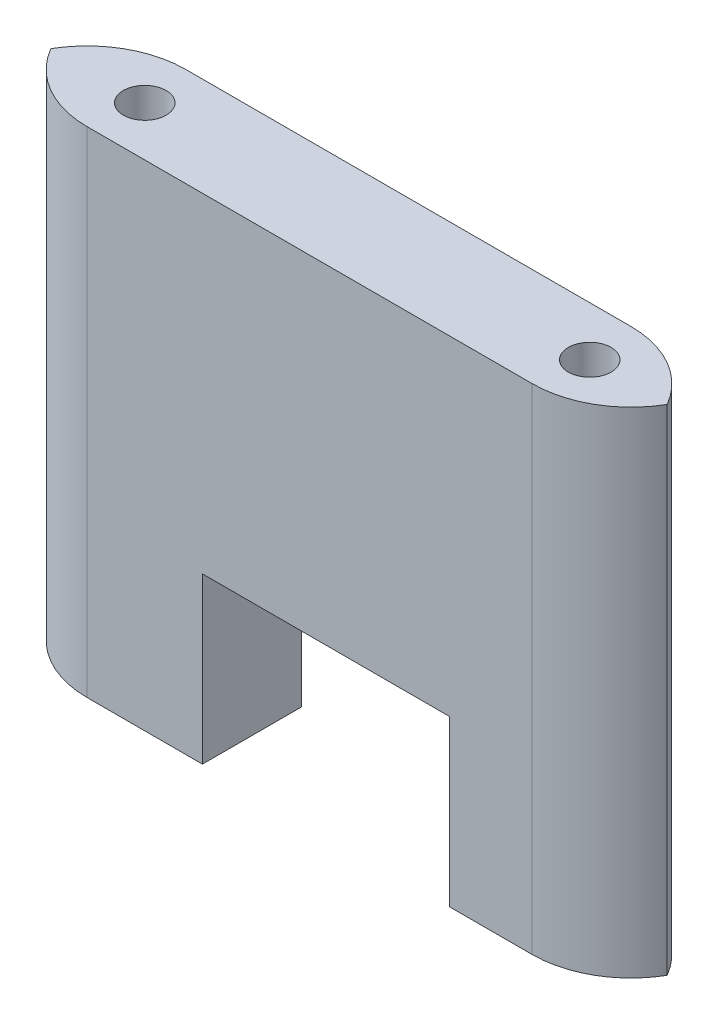
SolidWorks part; units mm, degrees
ref_plane "Front Plane" through (0, 0, 0) normal (0, 0, 1) x (1, 0, 0)
ref_plane "Top Plane" through (0, 0, 0) normal (0, 1, 0) x (1, 0, 0)
ref_plane "Right Plane" through (0, 0, 0) normal (1, 0, 0) x (0, 0, -1)
sketch "Sketch3" plane through (0, 0, 0) normal (0, 0, 1) x (1, 0, 0)
  line L1 (0, 0) -> (49.53, 0)
  line L2 (0, 0) -> (0, 38.1)
  line L3 (0, 38.1) -> (49.53, 38.1)
  line L4 (49.53, 0) -> (49.53, 38.1)
  dimension "D1" = 49.53
  dimension "D2" = 38.1
extrude "Boss-Extrude2" add sketch "Sketch3" along normal blind 7.62
sketch "Sketch4" plane through (0, 0, 7.62) normal (0, 0, 1) x (1, 0, 0)
  line L0 (26.035, 38.1) -> (26.035, -1.144) construction
  line L2 (0, 0) -> (49.53, 0) construction
  line L3 (16.51, 12.7) -> (35.56, 12.7)
  line L4 (16.51, 12.7) -> (16.51, 0)
  line L5 (16.51, 0) -> (35.56, 0)
  line L6 (35.56, 12.7) -> (35.56, 0)
  line L7 (16.51, 12.7) -> (35.56, 0) construction
  line L8 (16.51, 0) -> (35.56, 12.7) construction
  point P1 (26.035, 18.478)
  point P2 (26.035, 6.35)
  dimension "D1" = 26.035
  dimension "D2" = 19.05
  dimension "D3" = 12.7
extrude "Cut-Extrude1" cut sketch "Sketch4" against normal through all
ref_plane "Plane1" through (0, 19.05, 0) normal (0, 1, 0) x (1, 0, 0)
sketch "Sketch6" plane through (0, 0, 0) normal (0, -1, 0) x (1, 0, 0)
  line L0 (0, 7.62) -> (0, 0) construction
  line L1 (0, 7.62) -> (16.51, 7.62) construction
  line L2 (35.56, 0) -> (49.53, 0) construction
  line L3 (49.53, 7.62) -> (49.53, 0) construction
  circle A0 centre (8.255, 3.81) radius 1.651
  circle A1 centre (42.545, 3.81) radius 1.651
  point P5 (0, 3.81)
  point P8 (8.255, 7.62)
  point P12 (42.545, 0)
  point P15 (49.53, 3.81)
  dimension "D1" = 3.302
  dimension "D2" = 3.302
sketch "Sketch8" plane through (0, 38.1, 0) normal (0, 1, 0) x (1, 0, 0)
  circle A0 centre (8.255, -3.81) radius 1.651
  circle A1 centre (8.255, -3.81) radius 1.651 construction
  circle A2 centre (42.545, -3.81) radius 1.651
  circle A3 centre (42.545, -3.81) radius 1.651 construction
extrude "Cut-Extrude2" cut sketch "Sketch6" against normal blind 5.08
extrude "Cut-Extrude3" cut sketch "Sketch8" against normal blind 5.08
fillet "Fillet3" radius 7.62 4 edges at (49.53, 19.05, 7.62) (49.53, 19.05, 0) (0, 19.05, 0) (0, 19.05, 7.62)
